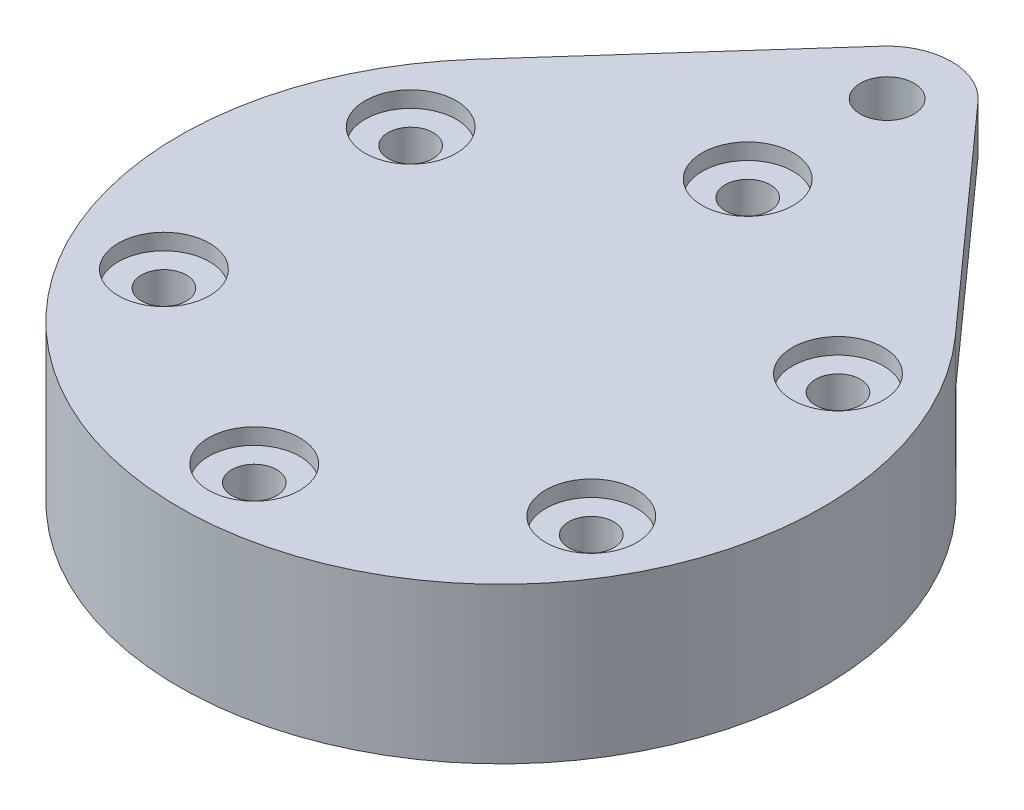
SolidWorks part; units mm, degrees
ref_plane "Front Plane" through (0, 0, 0) normal (0, 0, 1) x (1, 0, 0)
ref_plane "Top Plane" through (0, 0, 0) normal (0, 1, 0) x (1, 0, 0)
ref_plane "Right Plane" through (0, 0, 0) normal (1, 0, 0) x (0, 0, -1)
sketch "Sketch1" plane through (0, 0, 0) normal (0, 1, 0) x (1, 0, 0)
  line L0 (-4.4721, 40) -> (-22.3607, 20)
  line L1 (4.4721, 40) -> (22.3607, 20)
  circle A0 centre (0, 0) radius 36 construction
  circle A1 centre (0, 36) radius 2.5
  circle A2 centre (0, 36) radius 6
  circle A3 centre (0, 0) radius 23 construction
  circle A4 centre (0, 0) radius 30
  point P26 (0, 0)
  dimension "D1" = 60
  dimension "D2" = 5
  dimension "D3" = 46
  dimension "D4" = 12
extrude "Boss-Extrude1" add sketch "Sketch1" along normal blind 4.5 contours A4 | A4 L1 A2 | A4 A2 L0 | A2 A1 region at (-9.5087, 0, -30.8059) region at (0, 0, -41.8303) region at (0, 0, 0) region at (9.5087, 0, -30.8059)
sketch "Sketch2" plane through (0, 4.5, 0) normal (0, 1, 0) x (1, 0, 0)
  circle A0 centre (0, 0) radius 23 construction
  circle A1 centre (0, 23) radius 4.25
  circle A2 centre (19.9186, 11.5) radius 4.25
  circle A3 centre (19.9186, -11.5) radius 4.25
  circle A4 centre (0, -23) radius 4.25
  circle A5 centre (-19.9186, -11.5) radius 4.25
  circle A6 centre (-19.9186, 11.5) radius 4.25
  point P18 (0, 0)
  dimension "D1" = 8.5
  dimension "D2" = 6
extrude "Cut-Extrude1" cut sketch "Sketch2" against normal blind 1.5
sketch "Sketch3" plane through (0, 0, 0) normal (0, -1, 0) x (1, 0, 0)
  circle A0 centre (0, 0) radius 30
  dimension "D1" = 60
extrude "Boss-Extrude2" add sketch "Sketch3" along normal blind 10
sketch "Sketch4" plane through (0, 4.5, 0) normal (0, 1, 0) x (1, 0, 0)
  circle A0 centre (0, 0) radius 23 construction
  circle A1 centre (0, 23) radius 2.1
  circle A2 centre (19.9186, 11.5) radius 2.1
  circle A3 centre (19.9186, -11.5) radius 2.1
  circle A4 centre (0, -23) radius 2.1
  circle A5 centre (-19.9186, -11.5) radius 2.1
  circle A6 centre (-19.9186, 11.5) radius 2.1
  point P18 (0, 0)
  dimension "D1" = 4.2
extrude "Cut-Extrude2" cut sketch "Sketch4" against normal blind 43
